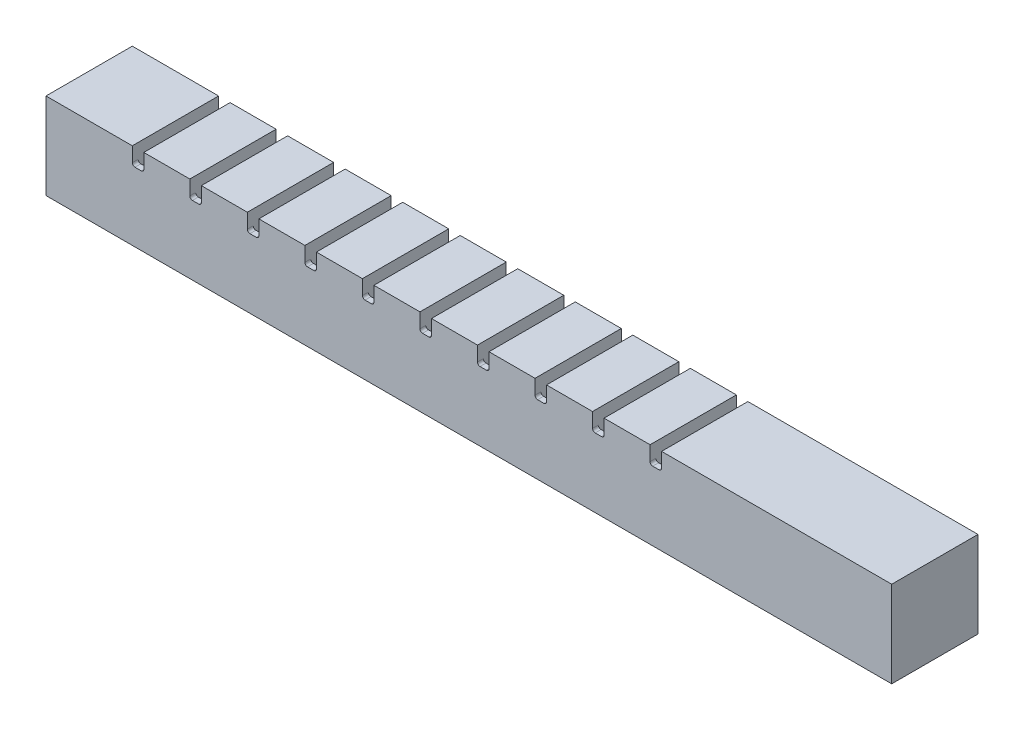
SolidWorks part; units mm, degrees
ref_plane "Front Plane" through (0, 0, 0) normal (0, 0, 1) x (1, 0, 0)
ref_plane "Top Plane" through (0, 0, 0) normal (0, 1, 0) x (1, 0, 0)
ref_plane "Right Plane" through (0, 0, 0) normal (1, 0, 0) x (0, 0, -1)
sketch "Sketch1" plane through (0, 0, 0) normal (0, 0, 1) x (1, 0, 0)
  line L1 (0, 0) -> (8, 0)
  line L2 (0, 0) -> (0, 15)
  line L3 (0, 15) -> (8, 15)
  line L4 (8, 0) -> (8, 15)
  dimension "D1" = 8
  dimension "D2" = 15
extrude "first chamber block" add sketch "Sketch1" along normal blind 15
sketch "Sketch2" plane through (0, 0, 0) normal (0, -1, 0) x (1, 0, 0)
  line L0 (8, 15) -> (8, 0) construction
  line L1 (1, 13) -> (7, 13)
  line L2 (1, 13) -> (1, 2)
  line L3 (1, 2) -> (7, 2)
  line L4 (7, 13) -> (7, 2)
  line L5 (0, 15) -> (0, 0) construction
  line L6 (0, 15) -> (8, 15) construction
  line L7 (0, 0) -> (8, 0) construction
  dimension "D1" = 1
  dimension "D2" = 1
  dimension "D3" = 2
  dimension "D4" = 2
extrude "first chamber cavity" cut sketch "Sketch2" against normal blind 13
sketch "Sketch3" plane through (8, 0, 0) normal (1, 0, 0) x (0, 0, -1)
  line L0 (-15, 0) -> (-15, 15) construction
  line L1 (0, 0) -> (-15, 0)
  line L2 (0, 0) -> (0, 3)
  line L3 (0, 3) -> (-15, 3)
  line L4 (-15, 0) -> (-15, 3)
  dimension "D1" = 3
extrude "chamber spacer" add sketch "Sketch3" along normal blind 2
pattern_linear "pattern chambers" count 11 spacing 10 along (1, 0, 0) of "chamber spacer", "first chamber cavity", "first chamber block"
combine bodies "combine into 1 solid body" operation type add bodies to combine 123 122 121 120 119 118 117 116 115 114 103
sketch "Sketch4" plane through (108, 0, 0) normal (1, 0, 0) x (0, 0, -1)
  line L1 (0, 15) -> (-15, 15)
  line L2 (0, 15) -> (0, 3)
  line L3 (0, 3) -> (-15, 3)
  line L4 (-15, 15) -> (-15, 3)
extrude "thicken end 1" add sketch "Sketch4" along normal up to surface (2 mm away) up to face at (110, 1.5, 7.5)
sketch "Sketch5" plane through (0, 0, 0) normal (-1, 0, 0) x (0, 0, 1)
  line L1 (15, 15) -> (0, 15)
  line L2 (15, 15) -> (15, 0)
  line L3 (15, 0) -> (0, 0)
  line L4 (0, 15) -> (0, 0)
extrude "thicken end 2" add sketch "Sketch5" along normal blind 2
ref_point "center of bottom face"
sketch "Sketch6" plane through (0, 0, 0) normal (0, -1, 0) x (1, 0, 0)
  line L0 (7, 2) -> (7, 13) construction
  line L1 (101, 6.5) -> (7, 6.5)
  line L2 (101, 6.5) -> (101, 8.5)
  line L3 (101, 8.5) -> (7, 8.5)
  line L4 (7, 6.5) -> (7, 8.5)
  line L5 (101, 6.5) -> (7, 8.5) construction
  line L6 (101, 8.5) -> (7, 6.5) construction
  point P0 (54, 7.5)
  dimension "D1" = 2
extrude "central air channel" cut sketch "Sketch6" against normal blind 2
sketch "Skizze3" plane through (8, 0, 0) normal (1, 0, 0) x (0, 0, -1)
  line L0 (-15, 3) -> (-13.5, 3)
  line L1 (0, 3) -> (-15, 3) construction
  line L2 (-13.5, 3) -> (-14, 12.5)
  line L3 (-14, 12.5) -> (-15, 12.5)
  line L4 (-15, 3) -> (-15, 15) construction
  line L5 (-15, 12.5) -> (-15, 3)
  line L6 (-7.5, 15) -> (-7.5, -49985) construction
  line L7 (-15, 15) -> (0, 15) construction
  line L8 (0, 12.5) -> (0, 3)
  line L9 (-1, 12.5) -> (0, 12.5)
  line L10 (-1.5, 3) -> (-1, 12.5)
  line L11 (0, 3) -> (-1.5, 3)
  point P13 (-7.5, 15)
  dimension "D1" = 2.5
  dimension "D2" = 1.5
  dimension "D3" = 1
extrude "Aufsatz-Linear austragen3" add sketch "Skizze3" along normal up to next
sketch "Skizze5" plane through (0, 0, 0) normal (0, 0, -1) x (-1, 0, 0)
  line L0 (-10, 12.5) -> (-10, 3) construction
  line L1 (-10, 12.5) -> (-8, 12.5) construction
  line L2 (-8, 12.5) -> (-8, 3) construction
  line L3 (-10, 12.5) -> (-10, 3) construction
  line L4 (-10, 12.5) -> (-8, 12.5) construction
  line L5 (-8, 12.5) -> (-8, 3) construction
  line L7 (-10, 12.5) -> (-8, 12.5)
  line L8 (-10, 12.5) -> (-10, 12.45)
  line L9 (-9.55, 12) -> (-8.45, 12)
  line L10 (-8, 12.5) -> (-8, 12.45)
  arc A0 (-8.45, 12) -> (-8, 12.45) centre (-8.45, 12.45) ccw
  arc A1 (-10, 12.45) -> (-9.55, 12) centre (-9.55, 12.45) ccw
  point P9 (-8, 12)
  dimension "D1" = 0.45
  dimension "D2" = 0.5
extrude "Schnitt-Linear austragen2" cut sketch "Skizze5" against normal through all
pattern_linear "Lineares Muster8" count 10 spacing 10 along (1, 0, 0) of "Aufsatz-Linear austragen3", "Schnitt-Linear austragen2"
sketch "Sketch17" plane through (110, 0, 0) normal (1, 0, 0) x (0, 0, -1)
  line L4 (0, 0) -> (0, 15)
  line L5 (0, 15) -> (-15, 15)
  line L6 (-15, 15) -> (-15, 0)
  line L7 (-15, 0) -> (0, 0)
  line L8 (0, 0) -> (0, 15)
  line L9 (0, 15) -> (-15, 15)
  line L10 (-15, 15) -> (-15, 0)
  line L11 (-15, 0) -> (0, 0)
  dimension "D1" = 0
extrude "Boss-Extrude1" add sketch "Sketch17" along normal blind 30
sketch "Sketch18" plane through (-2, 0, 0) normal (-1, 0, 0) x (0, 0, 1)
  line L4 (15, 0) -> (15, 15)
  line L5 (15, 15) -> (0, 15)
  line L6 (0, 15) -> (0, 0)
  line L7 (0, 0) -> (15, 0)
  line L8 (15, 0) -> (15, 15)
  line L9 (15, 15) -> (0, 15)
  line L10 (0, 15) -> (0, 0)
  line L11 (0, 0) -> (15, 0)
  dimension "D1" = 0
extrude "Boss-Extrude2" add sketch "Sketch18" along normal blind 5
sketch "Sketch19" plane through (0, 0, 0) normal (0, -1, 0) x (1, 0, 0)
  line L0 (-7, 15) -> (140, 15) construction
  line L1 (140, 0) -> (107, 0) construction
  line L2 (140, 0) -> (140, 15) construction
  line L3 (140, 15) -> (107, 15) construction
  line L4 (107, 0) -> (107, 15) construction
  line L5 (138, 2) -> (109, 2)
  line L6 (109, 2) -> (109, 13)
  line L7 (138, 13) -> (109, 13)
  line L8 (138, 2) -> (138, 13)
  line L9 (107, 2) -> (107, 13) construction
  line L10 (131.8284, 7.5) -> (137.3284, 2)
  line L11 (134.5, 2) -> (130.4142, 6.0858)
  line L12 (123.5, 13) -> (118, 7.5)
  line L13 (131.8284, 7.5) -> (137.3284, 13)
  line L15 (120.6716, 13) -> (116.5858, 8.9142)
  line L16 (123.5, 15.8284) -> (111.0858, 3.4142) construction
  line L17 (136.668, 8.5647) -> (134.2315, 5.0969) construction
  line L18 (138, 2) -> (137.3284, 2) construction
  line L19 (134.5, 13) -> (130.4142, 8.9142)
  line L20 (123.5, 2) -> (118, 7.5)
  line L21 (137.3284, 2) -> (137.3284, -1.3796) construction
  line L23 (120.6716, 2) -> (116.5858, 6.0858)
  line L25 (138.3045, 7.4149) -> (134.5, 2) construction
  line L27 (130.4142, 6.0858) -> (126.3284, 2)
  line L28 (129, 7.5) -> (123.5, 13)
  line L29 (130.4142, 8.9142) -> (126.3284, 13)
  line L30 (134.5, 2) -> (123.5, 13) construction
  line L31 (129, 7.5) -> (123.5, 2)
  line L32 (134.2315, 5.0969) -> (123.5, 15.8284) construction
  line L33 (115.1716, 7.5) -> (109.6716, 2)
  line L34 (116.5858, 8.9142) -> (112.5, 13)
  line L35 (115.1716, 7.5) -> (109.6716, 13)
  line L36 (116.5858, 6.0858) -> (112.5, 2)
  line L37 (124.5, 3) -> (122.5, 3) construction
  line L38 (123.5, 13) -> (112.5, 2) construction
  line L39 (124.5, 3) -> (124.5, 12)
  line L40 (124.5, 12) -> (122.5, 12) construction
  line L41 (122.5, 3) -> (122.5, 12)
  line L42 (109.6716, 2) -> (109.6716, -1.3796) construction
  line L43 (109, 2) -> (109, -1.3796) construction
  line L44 (138, -1.3796) -> (137.3284, -1.3796) construction
  line L45 (138, -1.3796) -> (138, 2) construction
  line L46 (137.3284, -1.3796) -> (109.6716, -1.3796) construction
  line L47 (109.6716, -1.3796) -> (109, -1.3796) construction
  line L48 (109.6716, 2) -> (109.6716, 13)
  line L49 (137.3284, 2) -> (137.3284, 13)
  dimension "D2" = 2
  dimension "D4" = 2
  dimension "D5" = 2
  dimension "D6" = 45
  dimension "D8" = 2
  dimension "D1" = 2
  dimension "D3" = 2
extrude "Cut-Extrude1" cut sketch "Sketch19" against normal offset from surface (12 mm away) 3 contours L13 L10 L5 L8 L7 | L11 L27 L5 | L29 L19 L7 | L23 L36 L5 | L34 L15 L7 | L33 L35 L6 | L39 L31 L28 | L20 L41 L12
